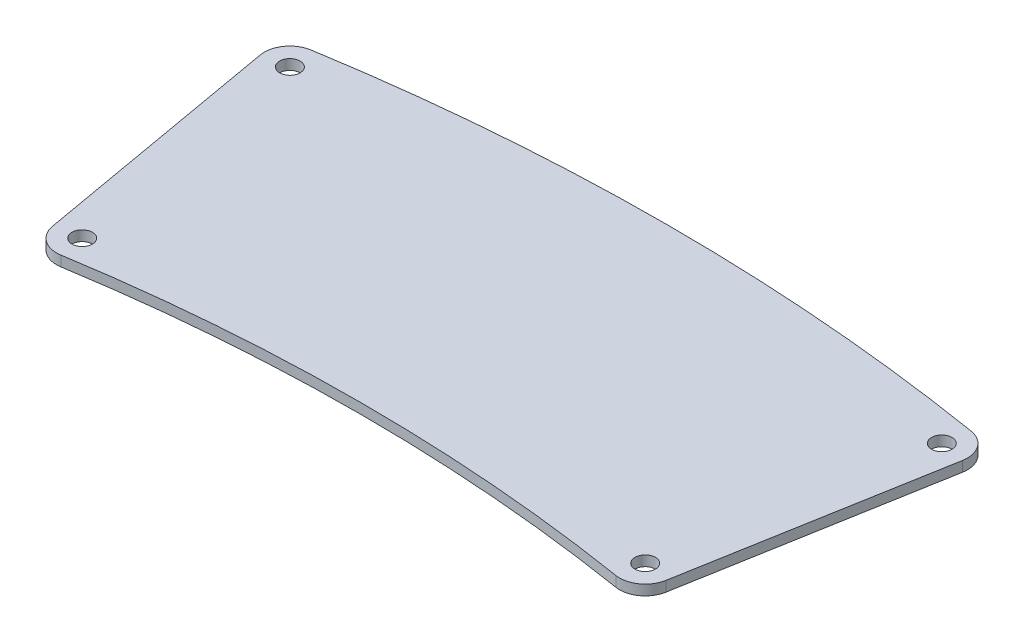
SolidWorks part; units mm, degrees
ref_plane "Спереди" through (0, 0, 0) normal (0, 0, 1) x (1, 0, 0)
ref_plane "Сверху" through (0, 0, 0) normal (0, 1, 0) x (1, 0, 0)
ref_plane "Справа" through (0, 0, 0) normal (1, 0, 0) x (0, 0, -1)
sketch "Эскиз1" plane through (0, 0, 0) normal (0, 1, 0) x (1, 0, 0)
  line L0 (-59.0404, 334.8346) -> (-69.4593, 393.9231) construction
  line L1 (0, 0) -> (0, 259.5027) construction
  line L2 (59.0404, 334.8346) -> (69.4593, 393.9231) construction
  line L3 (-59.0404, 334.8346) -> (-69.4593, 393.9231)
  line L4 (69.4593, 393.9231) -> (59.0404, 334.8346)
  line L10 (0, 400) -> (0, 340) construction
  line L11 (0, 0) -> (-69.4593, 393.9231) construction
  line L12 (0, 0) -> (69.4593, 393.9231) construction
  arc A0 (69.4593, 393.9231) -> (-69.4593, 393.9231) centre (0, 0) ccw construction
  arc A1 (69.4593, 393.9231) -> (-69.4593, 393.9231) centre (0, 0) ccw
  arc A2 (59.0404, 334.8346) -> (-59.0404, 334.8346) centre (0, 0) ccw
  dimension "D1" = 340
  dimension "D2" = 400
  dimension "D3" = 10
  dimension "D5" = 10
sheet metal parameters "Листовой металл1" thickness 2 parameters "D1"=1.2, "Толщина"=2
base flange "Базовая кромка1" sketch "Эскиз1" thickness 2 reverse thickness direction no parameters "D1"=1.2
fillet "Скругление1" radius 5 4 edges at (-59.0404, -1, -334.8346) (-69.4593, -1, -393.9231) (69.4593, -1, -393.9231) (59.0404, -1, -334.8346)
sketch "Эскиз2" plane through (0, 0, 0) normal (0, 1, 0) x (1, 0, 0)
  circle A0 centre (-63.6615, 389.8361) radius 2
  circle A1 centre (-54.9783, 340.5912) radius 2
  circle A2 centre (63.6615, 389.8361) radius 2
  circle A3 centre (54.9783, 340.5912) radius 2
  dimension "D1" = 4
  dimension "D2" = 4
  dimension "D3" = 4
  dimension "D4" = 4
extrude "Вырез-Вытянуть1" cut sketch "Эскиз2" against normal blind 10 normal cut yes
flat pattern "Развертка1" [suppressed]
sketch "Сгиб-Линии1" plane through (0, 0, 0) normal (0, 1, 0) x (1, 0, 0)
sketch3d "Граничная рамка1" [suppressed]
  line L0 (-105.7369, 160.0484, 0) -> (154.0999, 114.2321, 0) construction
  line L1 (-89.9793, 249.4139, 0) -> (169.8575, 203.5977, 0) construction
  line L2 (-105.7369, 160.0484, 0) -> (-89.9793, 249.4139, 0) construction
  line L3 (154.0999, 114.2321, 0) -> (169.8575, 203.5977, 0) construction
